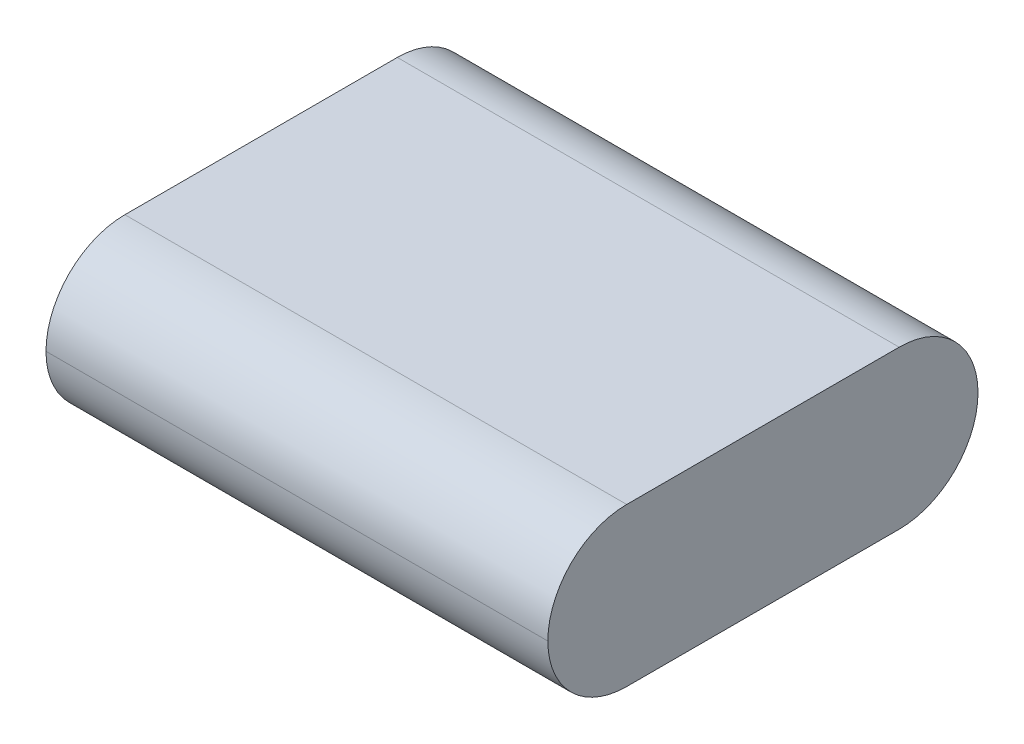
SolidWorks part; units mm, degrees
ref_plane "前视基准面" through (0, 0, 0) normal (0, 0, 1) x (1, 0, 0)
ref_plane "上视基准面" through (0, 0, 0) normal (0, 1, 0) x (1, 0, 0)
ref_plane "右视基准面" through (0, 0, 0) normal (1, 0, 0) x (0, 0, -1)
sketch "草图1" plane through (0, 0, 0) normal (0, 1, 0) x (1, 0, 0)
  line L1 (-35, -30) -> (35, -30)
  line L2 (-35, -30) -> (-35, 30)
  line L3 (-35, 30) -> (35, 30)
  line L4 (35, -30) -> (35, 30)
  line L5 (-35, -30) -> (35, 30) construction
  line L6 (-35, 30) -> (35, -30) construction
  point P0 (0, 0)
  dimension "D1" = 70
  dimension "D2" = 60
extrude "凸台-拉伸1" add sketch "草图1" along normal blind 22 contours L2 L1 L4 L3
fillet "圆角1" radius 11 4 edges at (0, 0, -30) (0, 22, -30) (0, 0, 30) (0, 22, 30)
